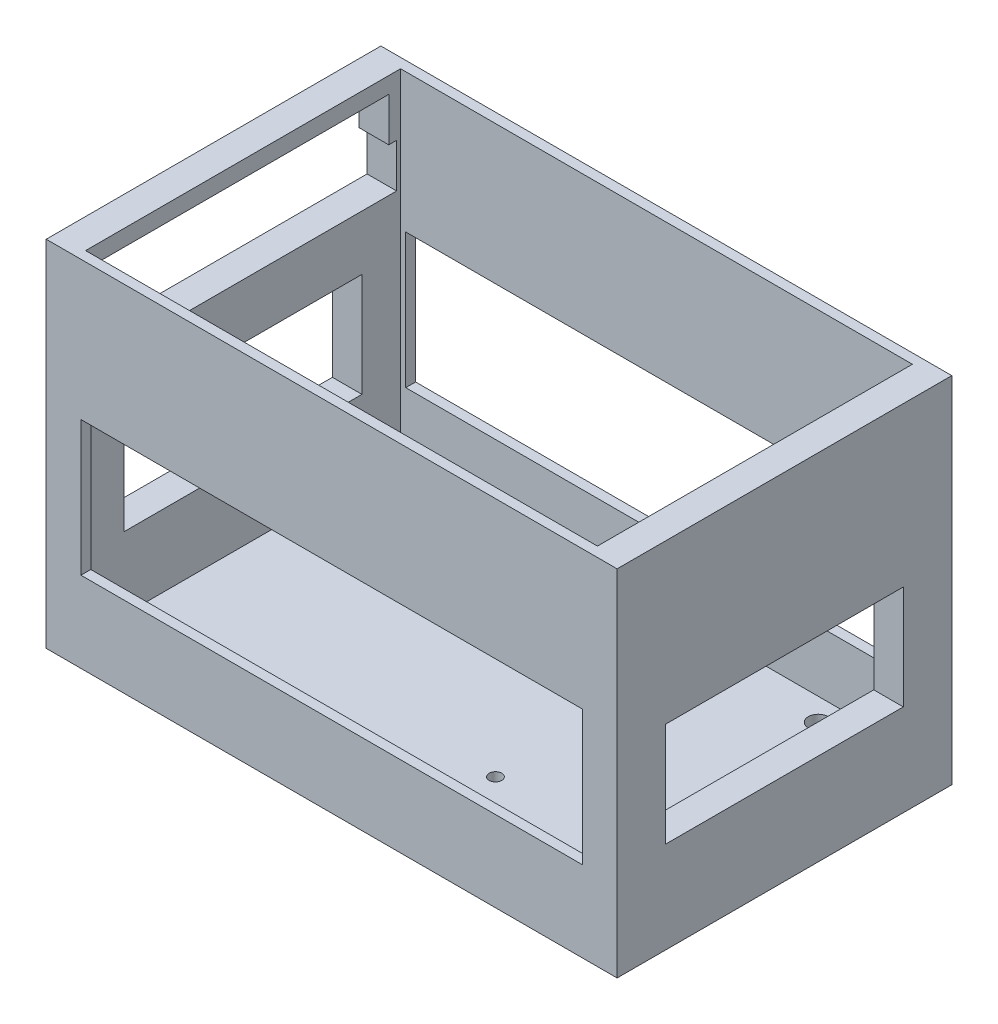
SolidWorks part; units mm, degrees
ref_plane "Front Plane" through (0, 0, 0) normal (0, 0, 1) x (1, 0, 0)
ref_plane "Top Plane" through (0, 0, 0) normal (0, 1, 0) x (1, 0, 0)
ref_plane "Right Plane" through (0, 0, 0) normal (1, 0, 0) x (0, 0, -1)
sketch "Sketch1" plane through (0, 0, 0) normal (0, 1, 0) x (1, 0, 0)
  line L1 (-72.5, -42.5) -> (72.5, -42.5)
  line L2 (-72.5, -42.5) -> (-72.5, 42.5)
  line L3 (-72.5, 42.5) -> (72.5, 42.5)
  line L4 (72.5, -42.5) -> (72.5, 42.5)
  line L5 (-72.5, -42.5) -> (72.5, 42.5) construction
  line L6 (-72.5, 42.5) -> (72.5, -42.5) construction
  point P0 (0, 0)
  dimension "D1" = 145
  dimension "D2" = 85
extrude "Boss-Extrude1" add sketch "Sketch1" along normal blind 90
sketch "Sketch3" plane through (0, 90, 0) normal (0, 1, 0) x (1, 0, 0)
  line L1 (-65, -40) -> (65, -40)
  line L2 (-65, -40) -> (-65, 40)
  line L3 (-65, 40) -> (65, 40)
  line L4 (65, -40) -> (65, 40)
  line L5 (-65, -40) -> (65, 40) construction
  line L6 (-65, 40) -> (65, -40) construction
  point P0 (0, 0)
  dimension "D1" = 130
  dimension "D2" = 80
extrude "Cut-Extrude1" cut sketch "Sketch3" against normal blind 85
sketch "Sketch4" plane through (0, 5, 0) normal (0, 1, 0) x (1, 0, 0)
  line L0 (-55, 0) -> (55, 0) construction
  line L1 (-61.1316, 34.1) -> (-61.1316, -34.1) construction
  line L2 (-61.1316, 34.1) -> (-8.7316, 34.1) construction
  line L3 (-8.7316, 34.1) -> (-8.7316, -34.1) construction
  line L4 (-61.1316, -34.1) -> (-8.7316, -34.1) construction
  line L5 (-61.1316, 34.1) -> (-8.7316, -34.1) construction
  line L6 (-8.7316, 34.1) -> (-61.1316, -34.1) construction
  point P0 (-34.9316, 0)
  dimension "D1" = 68.2
  dimension "D2" = 52.4
sketch "Sketch6" plane through (0, 5, 0) normal (0, 1, 0) x (1, 0, 0)
  line L0 (-55, 0) -> (55, 0) construction
  line L1 (62.5521, -24.9) -> (11.0521, -24.9) construction
  line L2 (62.5521, -24.9) -> (62.5521, 24.9) construction
  line L3 (62.5521, 24.9) -> (11.0521, 24.9) construction
  line L4 (11.0521, -24.9) -> (11.0521, 24.9) construction
  line L5 (62.5521, -24.9) -> (11.0521, 24.9) construction
  line L6 (62.5521, 24.9) -> (11.0521, -24.9) construction
  point P0 (36.8021, 0)
  dimension "D1" = 51.5
  dimension "D2" = 49.8
sketch "Sketch7" plane through (0, 5, 0) normal (0, 1, 0) x (1, 0, 0)
  line L0 (-55, 0) -> (55, 0) construction
  line L1 (-4.5845, -15.7) -> (7.4155, -15.7) construction
  line L2 (-4.5845, -15.7) -> (-4.5845, 15.7) construction
  line L3 (-4.5845, 15.7) -> (7.4155, 15.7) construction
  line L4 (7.4155, -15.7) -> (7.4155, 15.7) construction
  line L5 (-4.5845, -15.7) -> (7.4155, 15.7) construction
  line L6 (-4.5845, 15.7) -> (7.4155, -15.7) construction
  point P0 (1.4155, 0)
  dimension "D1" = 31.4
  dimension "D2" = 12
sketch "Sketch8" plane through (0, 5, 0) normal (0, 1, 0) x (1, 0, 0)
  line L0 (-54.6316, -32.1) -> (-26.6716, -32.1) construction
  line L1 (-8.7316, 34.1) -> (-11.2316, 34.1) construction
  line L2 (-8.7316, 34.1) -> (-8.7316, 18.71) construction
  line L3 (-8.7316, 18.71) -> (-11.2316, 18.71) construction
  line L4 (-11.2316, 34.1) -> (-11.2316, 18.71) construction
  line L5 (-61.1316, -34.1) -> (-8.7316, -34.1) construction
  line L6 (-62.1316, 20.42) -> (-59.6316, 20.42) construction
  line L7 (-59.6316, 34.1) -> (-59.6316, 20.42) construction
  line L8 (-62.1316, 34.1) -> (-59.6316, 34.1) construction
  line L9 (-62.1316, 34.1) -> (-62.1316, 20.42) construction
  line L10 (-62.1316, 34.1) -> (-54.6316, 34.1) construction
  line L11 (-62.1316, 34.1) -> (-62.1316, -32.1) construction
  line L12 (-62.1316, -32.1) -> (-54.6316, -32.1) construction
  line L13 (-54.6316, 34.1) -> (-54.6316, -32.1) construction
  line L14 (-8.7316, 34.1) -> (-8.7316, -34.1) construction
  circle A0 centre (-59.6316, 20.42) radius 1.7
  circle A1 centre (-11.2316, 18.71) radius 1.7
  circle A2 centre (-54.6316, -32.1) radius 1.7
  circle A3 centre (-26.6716, -32.1) radius 1.7
  dimension "D6" = 3.4
  dimension "D7" = 3.4
  dimension "D8" = 3.4
  dimension "D9" = 3.4
  dimension "D1" = 2.5
  dimension "D2" = 15.39
  dimension "D3" = 66.2
  dimension "D4" = 7.5
  dimension "D5" = 27.96
  dimension "D10" = 2
  dimension "D11" = 2.5
  dimension "D12" = 54.52
  dimension "D13" = 17.94
extrude "Cut-Extrude2" cut sketch "Sketch8" against normal blind 10
sketch "Sketch9" plane through (0, 5, 0) normal (0, 1, 0) x (1, 0, 0)
  line L0 (57.8021, 21.3) -> (17.8021, 21.3) construction
  line L1 (62.5521, 24.9) -> (57.8021, 24.9) construction
  line L2 (62.5521, 24.9) -> (62.5521, 21.3) construction
  line L3 (62.5521, 21.3) -> (57.8021, 21.3) construction
  line L4 (57.8021, 24.9) -> (57.8021, 21.3) construction
  circle A0 centre (57.8021, 21.3) radius 1.6
  circle A1 centre (17.8021, 21.3) radius 1.6
  circle A2 centre (17.8021, -18.7) radius 1.6
  circle A3 centre (57.8021, -18.7) radius 1.6
  dimension "D4" = 3.2
  dimension "D5" = 3.2
  dimension "D7" = 3.2
  dimension "D9" = 3.2
  dimension "D1" = 4.75
  dimension "D2" = 3.6
  dimension "D3" = 40
  dimension "D6" = 40
  dimension "D8" = 40
  dimension "D10" = 40
extrude "Cut-Extrude3" cut sketch "Sketch9" against normal blind 10
sketch "Sketch10" plane through (72.5, 0, 0) normal (1, 0, 0) x (0, 0, -1)
  line L0 (0, 55) -> (0, -55) construction
  line L1 (-30.1829, 23.2857) -> (30.1829, 23.2857)
  line L2 (-30.1829, 23.2857) -> (-30.1829, 49.6693)
  line L3 (-30.1829, 49.6693) -> (30.1829, 49.6693)
  line L4 (30.1829, 23.2857) -> (30.1829, 49.6693)
  line L5 (-30.1829, 23.2857) -> (30.1829, 49.6693) construction
  line L6 (-30.1829, 49.6693) -> (30.1829, 23.2857) construction
  point P0 (0, 36.4775)
extrude "Cut-Extrude4" cut sketch "Sketch10" against normal through all
sketch "Sketch11" plane through (0, 0, -42.5) normal (0, 0, -1) x (-1, 0, 0)
  line L0 (0, 46.75) -> (0, -46.75) construction
  line L1 (-63.6843, 20.506) -> (63.6843, 20.506)
  line L2 (-63.6843, 20.506) -> (-63.6843, 54.7549)
  line L3 (-63.6843, 54.7549) -> (63.6843, 54.7549)
  line L4 (63.6843, 20.506) -> (63.6843, 54.7549)
  line L5 (-63.6843, 20.506) -> (63.6843, 54.7549) construction
  line L6 (-63.6843, 54.7549) -> (63.6843, 20.506) construction
  point P0 (0, 37.6305)
extrude "Cut-Extrude5" cut sketch "Sketch11" against normal through all
sketch "Sketch12" plane through (-72.5, 0, 0) normal (-1, 0, 0) x (0, 0, 1)
  line L0 (0, -49.5) -> (0, 49.5) construction
  line L1 (-39, 63.6089) -> (39, 63.6089)
  line L2 (-39, 63.6089) -> (-39, 74.7589)
  line L3 (-37, 85.8589) -> (37, 85.8589)
  line L4 (39, 63.6089) -> (39, 74.7589)
  line L5 (-39, 63.6089) -> (37, 65.0986) construction
  line L6 (-37, 65.0986) -> (39, 63.6089) construction
  line L7 (39, 74.7589) -> (37, 74.7589)
  line L10 (-39, 74.7589) -> (-37, 74.7589)
  line L11 (-37, 85.8589) -> (-37, 74.7589)
  line L12 (37, 85.8589) -> (37, 74.7589)
  point P0 (0, 64.3734)
  dimension "D1" = 11.15
  dimension "D2" = 78
  dimension "D3" = 2
  dimension "D4" = 22.25
extrude "Cut-Extrude8" cut sketch "Sketch12" against normal blind 142
sketch "Sketch13" plane through (0, 0, 0) normal (0, -1, 0) x (1, 0, 0)
  line L0 (0, 34.2863) -> (46.7859, 34.2863) construction
  line L1 (0, -46.75) -> (0, 46.75) construction
  line L2 (49.5, 0) -> (-49.5, 0) construction
  circle A2 centre (46.7859, -34.2863) radius 2.5
  circle A3 centre (0, -34.2863) radius 2.5
  dimension "D1" = 46.7859
extrude "Cut-Extrude9" cut sketch "Sketch13" against normal blind 10
fillet "Fillet1" radius 5 2 edges at (69.5, 69.1839, -39) (69.5, 69.1839, 39)
